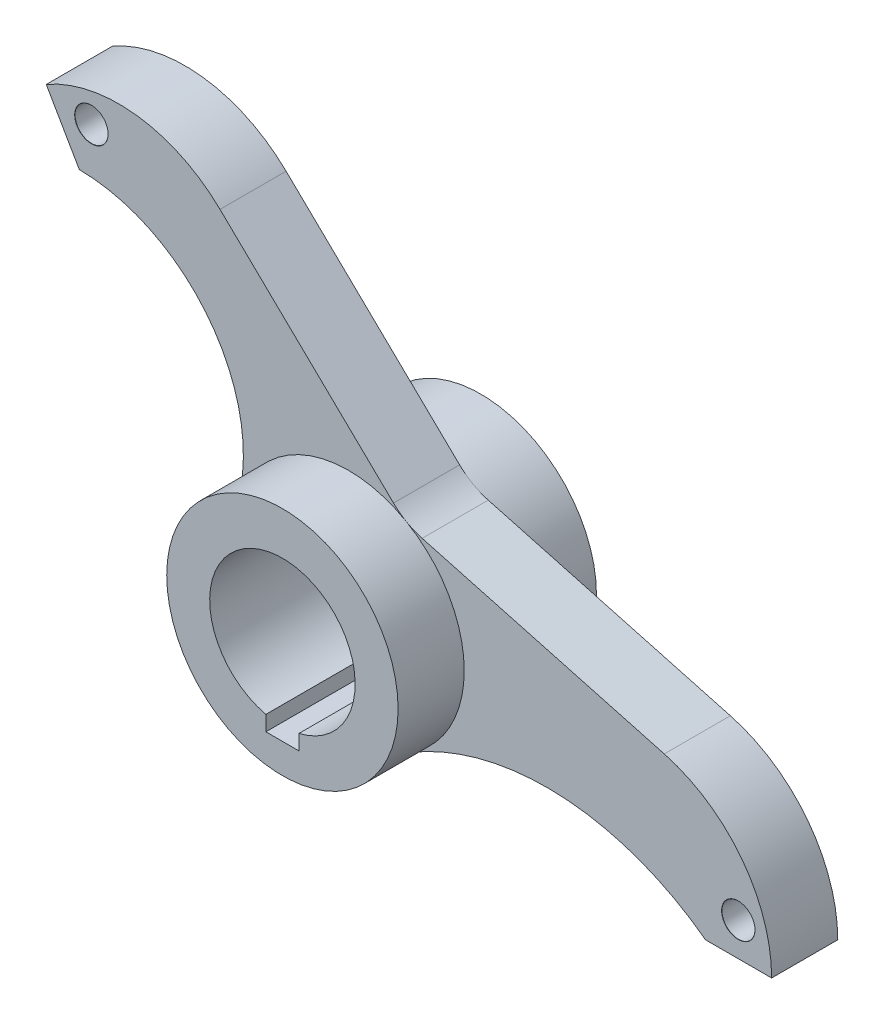
SolidWorks part; units mm, degrees
note: The reader was unsure of these and kept them because the rebuilt part matched: shared geometry of "Schizzo2<8>".
ref_plane "Piano frontale" through (0, 0, 0) normal (0, 0, 1) x (1, 0, 0)
ref_plane "Piano superiore" through (0, 0, 0) normal (0, 1, 0) x (1, 0, 0)
ref_plane "Piano destro" through (0, 0, 0) normal (1, 0, 0) x (0, 0, -1)
sketch "Schizzo2" plane through (0, 0, 0) normal (0, 0, 1) x (1, 0, 0)
  line L0 (59, 0) -> (0, 0) construction
  line L1 (0, 0) -> (-28.5, 49.3634) construction
  line L2 (-28.5, 49.3634) -> (-43.2224, 40.8634) construction
  line L3 (-40.7224, 36.5333) -> (-45.7224, 45.1936)
  line L4 (-38.8923, 43.3634) -> (-43.7801, 51.8293) construction
  line L5 (59, 0) -> (59, -17) construction
  line L6 (54, -17) -> (64, -17)
  line L7 (45.1661, -12) -> (59, -12) construction
  line L8 (-45.7224, 45.1936) -> (-25.0787, 57.1123) construction
  line L9 (-19.4396, 41.9661) -> (6.8032, 16.6225)
  line L10 (0, 0) -> (13.75, 23.8157) construction
  line L11 (11.1329, 14.1642) -> (47.7575, 4.2333)
  line L12 (64, -17) -> (64, 0.058) construction
  line L13 (0, 0) -> (0, -13) construction
  line L14 (-2.5, -13) -> (2.5, -13)
  line L15 (-2.5, -13) -> (-2.5, -10.7121)
  line L17 (2.5, -10.7121) -> (2.5, -13)
  circle A0 centre (0, 0) radius 17.5
  arc A1 (-40.7224, 36.5333) -> (-16.8432, 4.7493) centre (-40.905, 11.534) cw
  arc A2 (-45.7224, 45.1936) -> (-19.4396, 41.9661) centre (-34.7224, 26.141) cw
  arc A3 (6.8032, 16.6225) -> (11.1329, 14.1642) centre (13.75, 23.8157) ccw
  arc A4 (64, -17) -> (47.7575, 4.2333) centre (42, -17) ccw
  arc A5 (54, -17) -> (9.1424, -14.922) centre (30.0393, -49.0295) ccw
  arc A6 (2.5, -10.7121) -> (-2.5, -10.7121) centre (0, 0) ccw
  point P28 (0, 0)
  point P31 (45.1661, -12)
  point P32 (47.7575, 4.7493)
  point P35 (47.7575, 4.7493)
  point P36 (0, 0)
  point P38 (47.7575, 4.7493)
  point P39 (0, 0)
  point P40 (0, 0)
  dimension "D10" = 35
  dimension "D11" = 25
  dimension "D12" = 22
  dimension "D14" = 10
  dimension "D15" = 22
  dimension "D16" = 40
  dimension "D20" = 11
  dimension "D1" = 57
  dimension "D2" = 10
  dimension "D3" = 17
  dimension "D4" = 5
  dimension "D5" = 60
  dimension "D6" = 10
  dimension "D7" = 5
  dimension "D8" = 17
  dimension "D9" = 59
  dimension "D13" = 60
  dimension "D18" = 13
  dimension "D19" = 5
extrude "Estrusione-Estrusione2" add sketch "Schizzo2" along normal mid plane 30 contours A0 A6 L17 L14 L15
extrude "Estrusione-Estrusione3" add sketch "Schizzo2<8>" along normal mid plane 10 contours A3 L9 A2 L3 A1 A0 | A5 L6 A4 L11 A3 A0
sketch "Schizzo2<8>" plane through (0, 0, 0) normal (0, 0, 1) x (1, 0, 0) same geometry as "Schizzo2"
hole_wizard "Foro Ø5.0 (5)-1" positions "Schizzo3D2" profile "Schizzo7" hole size "Ø5.0" standard "ISO"
sketch3d "Schizzo3D2"
  point P0 (-38.8923, 43.3635, 5)
  point P13 (58.9561, -11.9548, 5)
  point P15 (59, -12, 0)
  point P19 (0, 0, 0)
sketch "Schizzo7" plane through (-38.8923, 43.3635, 5) normal (1, 0, 0) x (0, -1, 0)
  line L0 (0, 0) -> (0, 10)
  line L1 (0, 10) -> (2.5, 10)
  line L2 (2.5, 10) -> (2.5, 0.025)
  line L3 (2.5, 0.025) -> (2.525, 0)
  line L5 (2.525, 0) -> (0, 0)
  line L6 (-2.5, 0.025) -> (-2.525, 0) construction
  line L11 (0, -6.35) -> (0, 107.95) construction
  dimension "Thru Hole Dia." = 5
  dimension "Thru Hole Depth" = 10
  dimension "Near C'Sink Dia." = 5.05
  dimension "Near C'Sink Angle" = 90
